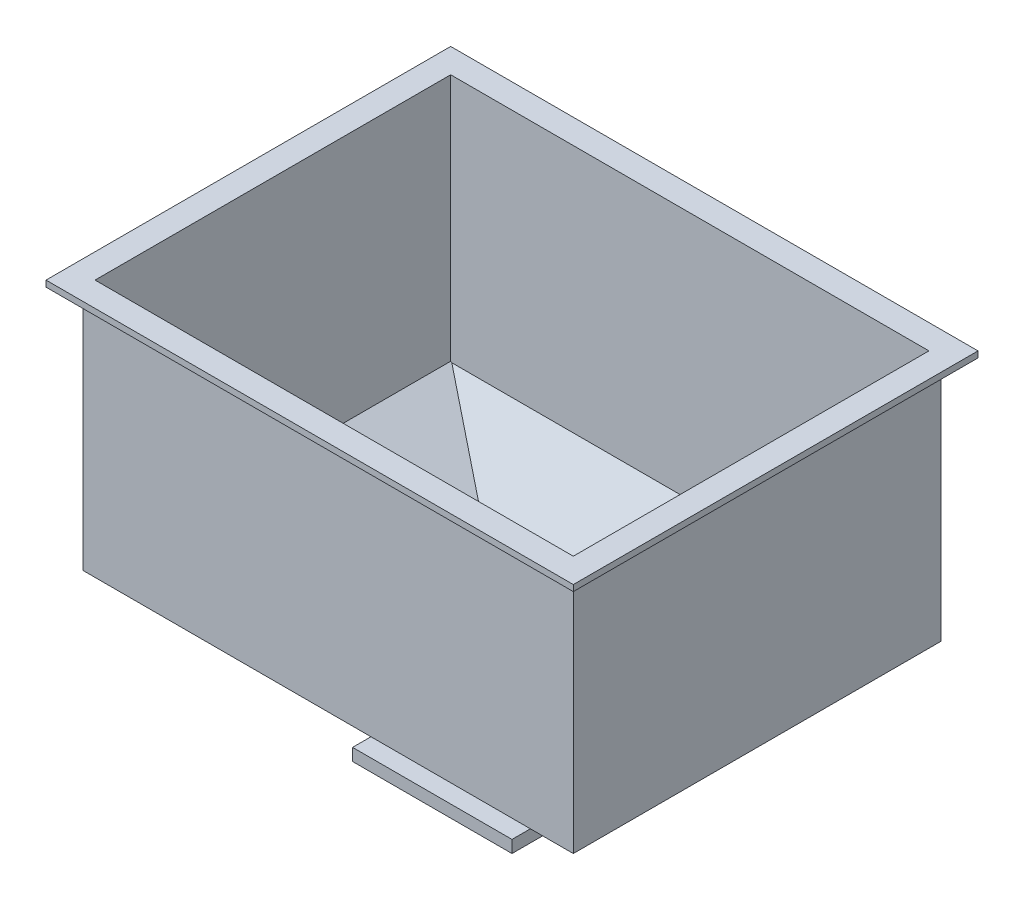
SolidWorks part; units mm, degrees
ref_plane "Front Plane" through (0, 0, 0) normal (0, 0, 1) x (1, 0, 0)
ref_plane "Top Plane" through (0, 0, 0) normal (0, 1, 0) x (1, 0, 0)
ref_plane "Right Plane" through (0, 0, 0) normal (1, 0, 0) x (0, 0, -1)
sketch "Sketch1" plane through (0, 0, 0) normal (0, 0, 1) x (1, 0, 0)
  line L0 (-200, -100) -> (-50, -200)
  line L1 (-200, 100) -> (200, 100)
  line L2 (-200, 100) -> (-200, -100)
  line L3 (-200, -100) -> (200, -100)
  line L4 (200, 100) -> (200, -100)
  line L5 (-50, -200) -> (50, -200)
  line L6 (50, -200) -> (200, -100)
  point P6 (0, -200)
  point P7 (0, -100)
  point P14 (200, 0)
  point P15 (0, 100)
  dimension "D1" = 200
  dimension "D2" = 400
  dimension "D3" = 100
  dimension "D4" = 100
extrude "Boss-Extrude1" add sketch "Sketch1" against normal blind 300 contours L4 L1 L2 L3 | L5 L6 L3 L0 region at (0, -140, 0) region at (0, 0, 0)
sketch "Sketch2" plane through (0, 0, 0) normal (1, 0, 0) x (0, 0, -1)
  line L0 (0, -100) -> (100, -200)
  line L1 (300, -200) -> (0, -200) construction
  line L2 (100, -200) -> (0, -200)
  line L3 (0, -200) -> (0, -100)
  line L4 (300, -100) -> (300, -200)
  line L5 (300, -200) -> (300, -100) construction
  line L6 (300, -200) -> (200, -200)
  line L7 (200, -200) -> (300, -100)
  dimension "D1" = 100
  dimension "D2" = 100
  dimension "D3" = 100
extrude "Cut-Extrude1" cut sketch "Sketch2" against normal through all both and the other way through all
shell "Shell1" thickness 5 removed face at (0, -200, -150) removed face at (0, 100, -150)
ref_plane "Plane1" through (0, 100, 0) normal (0, 1, 0) x (1, 0, 0)
sketch "Sketch3" plane through (0, 100, 0) normal (0, 1, 0) x (1, 0, 0)
  line L0 (-200, 0) -> (200, 0) construction
  line L1 (-215, 315) -> (215, 315)
  line L2 (-215, 315) -> (-215, -15)
  line L3 (-215, -15) -> (215, -15)
  line L4 (215, 315) -> (215, -15)
  line L5 (200, 300) -> (200, 0) construction
  point P6 (0, 0)
  point P7 (0, -15)
  point P8 (215, 150)
  point P11 (200, 150)
  dimension "D1" = 330
  dimension "D2" = 430
extrude "Boss-Extrude2" add sketch "Sketch3" along normal blind 5
shell "Shell2" thickness 5 removed face at (0, 100, -150) removed face at (0, 105, -150)
ref_plane "Plane5" through (0, -200, 0) normal (0, -1, 0) x (-1, 0, 0)
sketch "Sketch5" plane through (0, -200, 0) normal (0, -1, 0) x (1, 0, 0)
  line L0 (-50, -200) -> (-50, -100) construction
  line L1 (65, -215) -> (-65, -215)
  line L2 (65, -215) -> (65, -85)
  line L3 (65, -85) -> (-65, -85)
  line L4 (-65, -215) -> (-65, -85)
  line L8 (-50, -200) -> (50, -200) construction
  point P4 (-50, -150)
  point P7 (-65, -150)
  point P10 (0, -215)
  point P13 (0, -200)
  dimension "D1" = 130
  dimension "D2" = 130
extrude "Boss-Extrude3" add sketch "Sketch5" along normal blind 10
